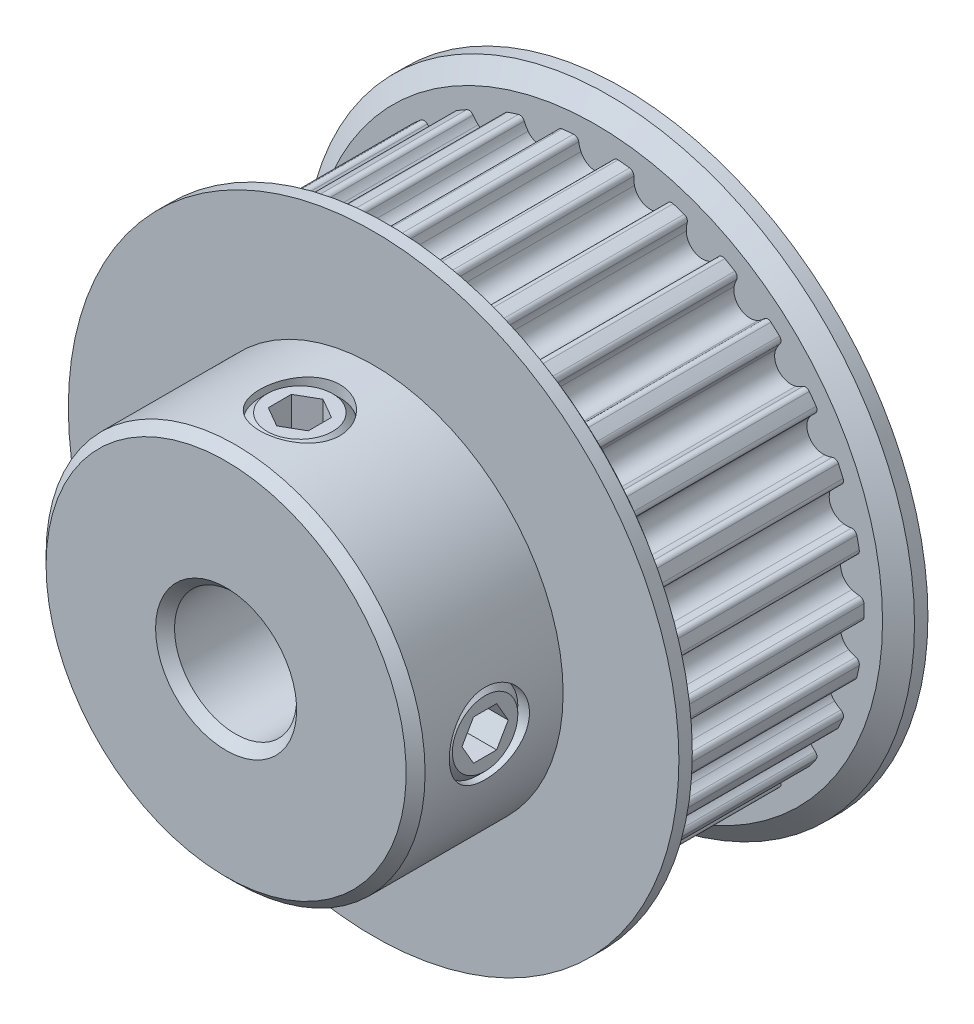
SolidWorks part; units mm, degrees
ref_plane "Front Plane" through (0, 0, 0) normal (0, 0, 1) x (1, 0, 0)
ref_plane "Top Plane" through (0, 0, 0) normal (0, 1, 0) x (1, 0, 0)
ref_plane "Right Plane" through (0, 0, 0) normal (1, 0, 0) x (0, 0, -1)
sketch "Sketch1" plane through (0, 0, 0) normal (0, 0, 1) x (1, 0, 0)
  line L1 (-2.7265, 12.8045) -> (2.7265, 12.8045) construction
  line L4 (0, 0) -> (0, 12.8045) construction
  line L5 (0, 12.8045) -> (0, 16.6915) construction
  line L6 (0, 14.3255) -> (2.9835, 14.0114) construction
  line L7 (2.9835, 14.0114) -> (4.1904, 13.7544) construction
  line L8 (2.9835, 14.0114) -> (2.7265, 12.8045) construction
  line L9 (-2.9835, 14.0114) -> (-2.7265, 12.8045) construction
  line L10 (-2.9042, 13.6387) -> (-3.3803, 15.875)
  line L11 (-3.3803, 15.875) -> (3.3803, 15.875)
  line L12 (3.3803, 15.875) -> (2.9042, 13.6387)
  circle A0 centre (0, 0) radius 14.3255 construction
  circle A1 centre (0, 0) radius 15.875 construction
  circle A2 centre (0, 0) radius 13.9445 construction
  arc A3 (-0.7739, 13.3029) -> (0.7739, 13.3029) centre (0, 13.6545) ccw
  arc A4 (-0.7739, 13.3029) -> (-0.8902, 13.6874) centre (0.61, 13.9316) cw
  arc A5 (-2.9042, 13.6387) -> (-1.1578, 13.8964) centre (0, 0) cw
  arc A6 (-0.8902, 13.6874) -> (-1.1578, 13.8964) centre (-1.137, 13.6472) ccw
  arc A7 (2.9042, 13.6387) -> (1.1578, 13.8964) centre (0, 0) ccw
  arc A8 (0.8902, 13.6874) -> (1.1578, 13.8964) centre (1.137, 13.6472) cw
  arc A9 (0.7739, 13.3029) -> (0.8902, 13.6874) centre (-0.61, 13.9316) ccw
  point P6 (0, 20.9083)
  point P11 (0, 14.3255)
  point P13 (0, 15.875)
  point P14 (0, 13.9445)
  dimension "D1" = 4.2168
  dimension "D2" = 2.366
sketch "Sketch2" plane through (0, 0, 0) normal (1, 0, 0) x (0, 0, -1)
  line L0 (-10.31, 3.175) -> (10.31, 3.175)
  line L1 (-10.31, 3.175) -> (-10.31, 9.855)
  line L2 (-10.31, 9.855) -> (-2.64, 9.855)
  line L3 (-2.64, 9.855) -> (-2.64, 15.875)
  line L4 (-2.64, 15.875) -> (-1.245, 15.875) construction
  line L5 (-1.245, 15.875) -> (-1.245, 13.9445) construction
  line L6 (-1.245, 13.9445) -> (8.915, 13.9445)
  line L7 (8.915, 13.9445) -> (8.915, 15.875) construction
  line L8 (8.915, 15.875) -> (10.31, 15.875) construction
  line L9 (10.31, 15.875) -> (10.31, 3.175)
  line L10 (-10.31, 0) -> (10.31, 0) construction
  line L11 (9.6125, 15.875) -> (8.915, 14.9097)
  line L12 (-1.245, 14.9097) -> (-1.9425, 15.875)
  line L13 (-2.64, 15.875) -> (-1.9425, 15.875)
  line L14 (-1.245, 14.9097) -> (-1.245, 13.9445)
  line L15 (8.915, 13.9445) -> (8.915, 14.9097)
  line L16 (9.6125, 15.875) -> (10.31, 15.875)
  arc A0 (-1.245, 14.9097) -> (-1.9425, 15.875) centre (-2.2616, 14.9097) ccw construction
  arc A1 (8.915, 14.9097) -> (9.6125, 15.875) centre (9.9316, 14.9097) cw construction
  point P12 (-1.245, 14.9097)
  point P14 (-1.9425, 15.875)
  point P20 (8.915, 14.9097)
  point P21 (9.6125, 15.875)
  point P25 (8.915, 0)
  point P26 (-1.245, 0)
revolve "Revolve1" add sketch "Sketch2" angle 360 mid plane about L10
sketch "Sketch3" plane through (0, 0, 0) normal (0, 0, 1) x (1, 0, 0)
  line L6 (3.3803, 15.875) -> (-3.3803, 15.875)
  line L7 (2.9042, 13.6387) -> (3.3803, 15.875)
  line L8 (-3.3803, 15.875) -> (-2.9042, 13.6387)
  line L9 (3.3803, 15.875) -> (-3.3803, 15.875)
  line L10 (2.9042, 13.6387) -> (3.3803, 15.875)
  line L11 (-3.3803, 15.875) -> (-2.9042, 13.6387)
  arc A8 (2.9042, 13.6387) -> (1.1578, 13.8964) centre (0, 0) ccw
  arc A9 (1.1578, 13.8964) -> (0.8902, 13.6874) centre (1.137, 13.6472) ccw
  arc A10 (0.7739, 13.3029) -> (0.8902, 13.6874) centre (-0.61, 13.9316) ccw
  arc A11 (-0.7739, 13.3029) -> (0.7739, 13.3029) centre (0, 13.6545) ccw
  arc A12 (-0.8902, 13.6874) -> (-0.7739, 13.3029) centre (0.61, 13.9316) ccw
  arc A13 (-0.8902, 13.6874) -> (-1.1578, 13.8964) centre (-1.137, 13.6472) ccw
  arc A14 (-1.1578, 13.8964) -> (-2.9042, 13.6387) centre (0, 0) ccw
  arc A15 (2.9042, 13.6387) -> (1.1578, 13.8964) centre (0, 0) ccw
  arc A16 (1.1578, 13.8964) -> (0.8902, 13.6874) centre (1.137, 13.6472) ccw
  arc A17 (0.7739, 13.3029) -> (0.8902, 13.6874) centre (-0.61, 13.9316) ccw
  arc A18 (-0.7739, 13.3029) -> (0.7739, 13.3029) centre (0, 13.6545) ccw
  arc A19 (-0.8902, 13.6874) -> (-0.7739, 13.3029) centre (0.61, 13.9316) ccw
  arc A20 (-0.8902, 13.6874) -> (-1.1578, 13.8964) centre (-1.137, 13.6472) ccw
  arc A21 (-1.1578, 13.8964) -> (-2.9042, 13.6387) centre (0, 0) ccw
  dimension "D1" = 0
extrude "Cut-Extrude1" cut sketch "Sketch3" against normal up to vertex (8.915 mm away) from vertex up to point (0, 13.9445, -8.915) starting at point (0, 13.9445, 1.245)
pattern_circular "CirPattern1" count 30 over 360 about axis through (0, 0, 10.31) along (0, 0, 1) of "Cut-Extrude1"
sketch "Sketch4" plane through (0, 0, 0) normal (1, 0, 0) x (0, -1, 0)
  line L0 (0, -2.64) -> (0, -10.31) construction
  line L1 (-9.855, -2.64) -> (9.855, -2.64) construction
  line L2 (-9.855, -10.31) -> (9.855, -10.31) construction
  circle A0 centre (0, -6.475) radius 2.0828
extrude "Cut-Extrude2" cut sketch "Sketch4" along normal through all
ref_plane "Plane1" through (0, 0, 6.475) normal (0, 0, 1) x (1, 0, 0)
sketch "Sketch5" plane through (0, 0, 6.475) normal (0, 0, 1) x (1, 0, 0)
  line L0 (0, 0.1664) -> (0, 9.855) construction
  line L1 (3.175, -1.7018) -> (3.175, 0)
  line L2 (3.556, -2.0828) -> (9.2514, -2.0828)
  line L3 (3.175, 0) -> (9.855, 0) construction
  line L4 (3.175, 0) -> (9.6324, 0)
  line L5 (9.6324, 0) -> (9.6324, -1.7018)
  line L6 (3.556, -2.0828) -> (3.175, -1.7018)
  line L7 (9.6324, -1.7018) -> (9.2514, -2.0828)
  circle A0 centre (0, 0) radius 9.855 construction
  circle A1 centre (0, 0) radius 3.175 construction
  point P2 (3.175, -2.0828)
  point P11 (9.6324, -2.0828)
revolve "Revolve2" add sketch "Sketch5" angle 360 mid plane about L4
sketch "Sketch6" plane through (9.6324, 5.3841, 0) normal (-1, 0, 0) x (0, -1, 0)
  line L1 (5.3841, 7.6775) -> (4.3427, 7.0763)
  line L2 (4.3427, 7.0763) -> (4.3427, 5.8737)
  line L3 (4.3427, 5.8737) -> (5.3841, 5.2725)
  line L4 (5.3841, 5.2725) -> (6.4255, 5.8737)
  line L5 (6.4255, 5.8737) -> (6.4255, 7.0763)
  line L6 (6.4255, 7.0763) -> (5.3841, 7.6775)
  circle A0 centre (5.3841, 6.475) radius 1.0414 construction
  dimension "D1" = 2.0828
extrude "Cut-Extrude3" cut sketch "Sketch6" along normal blind 1.5621
pattern_circular "CirPattern2" count 2 over 90 about axis through (0, 0, 10.31) along (0, 0, 1) of "Cut-Extrude2", "Revolve2", "Cut-Extrude3"
chamfer "Chamfer1" distance 0.4928 angle 45 2 edges at (3.175, 0, 10.31) (9.855, 0, 10.31)
ref_axis "Center Axis 1" through (0, 0, -10.31) along (0, 0, 1)
ref_plane "Contact Plane 1" through (0, 0, 10.31) normal (0, 0, 1) x (1, 0, 0)
ref_plane "Contact Plane 2" through (0, 0, -10.31) normal (0, 0, -1) x (-1, 0, 0)
equation "\"D2@Sketch1\" = \"D1@Sketch1\"/2"
equation "\"D1@Sketch6\" = \"Set Screw@Sketch4\" / 2"
equation "\"D1@Cut-Extrude3\" = \"D1@Sketch6\"*.75"
equation "\"D1@Chamfer1\"=\"Hub Dia@Sketch2\"*.025"
